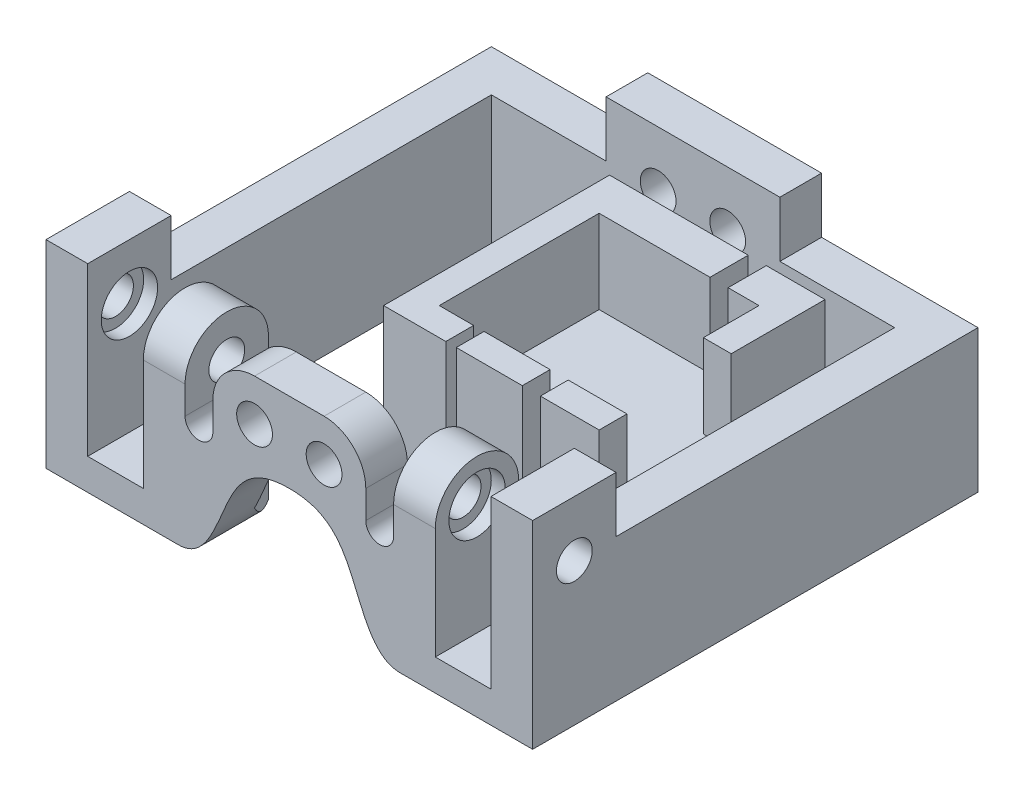
SolidWorks part; units mm, degrees
ref_plane "Front Plane" through (0, 0, 0) normal (0, 0, 1) x (1, 0, 0)
ref_plane "Top Plane" through (0, 0, 0) normal (0, 1, 0) x (1, 0, 0)
ref_plane "Right Plane" through (0, 0, 0) normal (1, 0, 0) x (0, 0, -1)
sketch "Sketch1" plane through (0, 0, 0) normal (0, 1, 0) x (1, 0, 0)
  line L0 (-29, 39) -> (-29, -39)
  line L1 (-35, 45) -> (35, 45)
  line L2 (-35, 45) -> (-35, -45)
  line L3 (-35, -45) -> (35, -45)
  line L4 (35, 45) -> (35, -45)
  line L5 (-29, -39) -> (29, -39)
  line L6 (29, 39) -> (29, -39)
  line L7 (-29, 39) -> (29, 39)
  point P4 (0, 45)
  point P5 (35, 0)
  point P7 (35, 27.1086)
  dimension "D1" = 70
  dimension "D2" = 90
  dimension "D3" = 6
extrude "Boss-Extrude1" add sketch "Sketch1" against normal blind 20.5
sketch "Sketch2" plane through (0, 0, 0) normal (0, -1, 0) x (-1, 0, 0)
  line L0 (-35, 45) -> (35, 45) construction
  line L1 (-12.5, 45) -> (12.5, 45)
  line L2 (-12.5, 45) -> (-12.5, 39)
  line L3 (-12.5, 39) -> (12.5, 39)
  line L4 (12.5, 45) -> (12.5, 39)
  line L5 (-29, 39) -> (29, 39) construction
  point P8 (0, 45)
  point P9 (0, 45)
  dimension "D1" = 25
extrude "Boss-Extrude2" add sketch "Sketch2" against normal blind 8
sketch "Sketch3" plane through (0, 0, -45) normal (0, 0, -1) x (-1, 0, 0)
  line L0 (0, 8) -> (0, 0) construction
  line L1 (12.5, 8) -> (-12.5, 8) construction
  circle A0 centre (-5, 0) radius 2.575
  circle A1 centre (5, 0) radius 2.575
  point P7 (0, 0)
  point P9 (-3.0953, 7.2588)
  point P14 (-18.5119, -15)
  dimension "D1" = 5.15
  dimension "D2" = 5
extrude "Cut-Extrude1" cut sketch "Sketch3" against normal up to next
sketch "Sketch4" plane through (0, 0, -45) normal (0, 0, -1) x (-1, 0, 0)
  line L0 (0, 0) -> (0, 8) construction
  line L1 (-35, 0) -> (35, 0) construction
  line L2 (12.5, 8) -> (-12.5, 8) construction
  circle A0 centre (-5, 0) radius 4.05
  circle A1 centre (-5, 0) radius 2.575 construction
  circle A2 centre (5, 0) radius 4.05
  dimension "D1" = 8.1
extrude "Cut-Extrude2" cut sketch "Sketch4" against normal blind 2
sketch "Sketch5" plane through (0, -20.5, 0) normal (0, 1, 0) x (1, 0, 0)
  line L0 (29, 39) -> (-29, 39) construction
  line L1 (-8, 33.5) -> (15, 33.5)
  line L2 (-8, 33.5) -> (-8, 10.5)
  line L3 (-8, 10.5) -> (15, 10.5)
  line L4 (15, 33.5) -> (15, 10.5)
  line L6 (29, -39) -> (29, 39) construction
  dimension "D1" = 23
  dimension "D2" = 23
  dimension "D3" = 5.5
  dimension "D4" = 14
extrude "Boss-Extrude3" add sketch "Sketch5" along normal offset from surface (7 mm away) 13.5 separate body up to face at (0, 0, -14)
sketch "Sketch16" plane through (0, -20.5, 0) normal (0, -1, 0) x (1, 0, 0)
  line L0 (29, -39) -> (12.5, -39) construction
  line L1 (19, -39) -> (-12, -39)
  line L2 (19, -39) -> (19, -6.5)
  line L3 (19, -6.5) -> (-12, -6.5)
  line L4 (-8, -33.5) -> (15, -33.5)
  line L5 (-8, -10.5) -> (-8, -33.5)
  line L6 (15, -10.5) -> (-8, -10.5)
  line L7 (15, -33.5) -> (15, -10.5)
  line L8 (-8, -33.5) -> (15, -33.5)
  line L9 (-8, -10.5) -> (-8, -33.5)
  line L10 (15, -10.5) -> (-8, -10.5)
  line L11 (15, -33.5) -> (15, -10.5)
  line L12 (-12, -39) -> (-12, -6.5)
  dimension "D2" = 4
  dimension "D3" = 4
  dimension "D4" = 4
  dimension "D1" = 0
extrude "Boss-Extrude6" add sketch "Sketch16" against normal offset from surface (19 mm away) 12 up to face at (3.5, -13.5, -22) offset beyond the face yes
sketch "Sketch18" plane through (0, -1.5, 0) normal (0, 1, 0) x (1, 0, 0)
  line L0 (15, 33.5) -> (-8, 33.5) construction
  line L1 (7.95, 33.5) -> (10.55, 33.5)
  line L2 (7.95, 33.5) -> (7.95, 39)
  line L3 (7.95, 39) -> (10.55, 39)
  line L4 (10.55, 33.5) -> (10.55, 39)
  line L5 (7.093, 39) -> (19, 39) construction
  line L6 (19, 6.5) -> (-12, 6.5) construction
  line L7 (7.95, 6.5) -> (10.55, 6.5)
  line L8 (7.95, 6.5) -> (7.95, 10.5)
  line L9 (7.95, 10.5) -> (10.55, 10.5)
  line L10 (10.55, 6.5) -> (10.55, 10.5)
  line L11 (-8, 10.5) -> (15, 10.5) construction
  line L12 (15, 10.5) -> (-8, 10.5) construction
  line L13 (-3.05, 6.5) -> (-1.55, 6.5)
  line L14 (-3.05, 6.5) -> (-3.05, 10.5)
  line L15 (-3.05, 10.5) -> (-1.55, 10.5)
  line L16 (-1.55, 6.5) -> (-1.55, 10.5)
  line L17 (19, 39) -> (19, 6.5) construction
  line L18 (15, 10.5) -> (19, 10.5)
  line L19 (15, 10.5) -> (15, 25.5)
  line L20 (15, 25.5) -> (19, 25.5)
  line L21 (19, 10.5) -> (19, 25.5)
  line L22 (15, 10.5) -> (15, 33.5) construction
  point P31 (7.95, 36.25)
  dimension "D1" = 15
  dimension "D2" = 4.45
  dimension "D3" = 2.6
  dimension "D4" = 9.5
  dimension "D5" = 1.5
extrude "Cut-Extrude10" cut sketch "Sketch18" against normal up to surface (12 mm away) up to face at (3.5, -13.5, -22)
sketch "gear_alignment_sketch" plane through (35, 0, 0) normal (1, 0, 0) x (0, 0, -1)
  line L0 (16.5, 0) -> (16.5, -20.5) construction
  line L1 (-45, 0) -> (45, 0) construction
  line L2 (-45, -20.5) -> (45, -20.5) construction
  line L3 (-992.2945, 0) -> (49007.7055, 0) construction
  line L5 (-45, 0) -> (45, 0) construction
  line L7 (-13.0635, 0) -> (16.5, -7.5) construction
  line L8 (25.5, -13.5) -> (33.5, -13.5) construction
  point P7 (-13.0635, 0)
  point P10 (16.5, -7.5)
  point P11 (0, 0)
  dimension "D1" = 6
  dimension "D3" = 30.5
  dimension "D2" = 6
sketch "Sketch8" plane through (0, 0, 0) normal (0, 1, 0) x (1, 0, 0)
  line L0 (35, -200992.2945) -> (35, 249007.7055) construction
  line L1 (35, -7.0635) -> (29, -7.0635)
  line L2 (35, -7.0635) -> (35, -19.0635)
  line L3 (35, -19.0635) -> (29, -19.0635)
  line L4 (29, -7.0635) -> (29, -19.0635)
  line L5 (29, -39) -> (29, 39) construction
  dimension "D1" = 12
extrude "Boss-Extrude4" add sketch "Sketch8" along normal blind 8
sketch "Sketch7" plane through (35, 0, 0) normal (1, 0, 0) x (0, 0, -1)
  circle A0 centre (-13.0635, 0) radius 2.575
  dimension "D1" = 5.15
extrude "x" cut sketch "Sketch7" against normal up to next
sketch "Sketch9" plane through (29, 0, 0) normal (1, 0, 0) x (0, 0, -1)
  circle A0 centre (-13.0635, 0) radius 4.05
  dimension "D1" = 8.1
extrude "Cut-Extrude4" cut sketch "Sketch9" along normal blind 2
sketch "Sketch10" plane through (0, -20.5, 0) normal (0, -1, 0) x (1, 0, 0)
  line L1 (0, 7.0635) -> (29, 7.0635)
  line L3 (0, 19.0635) -> (29, 19.0635)
  line L4 (29, 7.0635) -> (29, 19.0635)
  line L5 (29, 39) -> (29, -39) construction
  line L6 (35, 7.0635) -> (29, 7.0635) construction
  line L7 (29, 19.0635) -> (35, 19.0635) construction
  line L8 (0, -1000) -> (0, 49000) construction
  line L9 (0, 7.0635) -> (0, 19.0635)
extrude "Boss-Extrude5" add sketch "Sketch10" against normal up to surface (28.5 mm away) up to face at (32, 8, 13.0635)
sketch "Sketch12" plane through (0, 8, 0) normal (0, 1, 0) x (1, 0, 0)
  line L0 (0, -19.0635) -> (35, -19.0635) construction
  line L1 (29, -7.0635) -> (21, -7.0635)
  line L2 (29, -7.0635) -> (29, -19.0635)
  line L3 (29, -19.0635) -> (21, -19.0635)
  line L4 (21, -7.0635) -> (21, -19.0635)
  line L5 (35, -7.0635) -> (0, -7.0635) construction
  line L6 (15, -7.0635) -> (0, -7.0635)
  line L7 (15, -7.0635) -> (15, -19.0635)
  line L8 (15, -19.0635) -> (0, -19.0635)
  line L9 (0, -7.0635) -> (0, -19.0635)
  dimension "D1" = 8
  dimension "D2" = 6
extrude "Cut-Extrude6" cut sketch "Sketch12" against normal blind 24
sketch "Sketch13" plane through (21, 0, 0) normal (1, 0, 0) x (0, 0, -1)
  circle A0 centre (-13.0635, 0) radius 2.575
  circle A1 centre (-13.0635, 0) radius 2.575 construction
extrude "Cut-Extrude7" cut sketch "Sketch13" against normal up to next
sketch "Sketch14" plane through (21, 0, 0) normal (1, 0, 0) x (0, 0, -1)
  circle A0 centre (-13.0635, 0) radius 4.05
  circle A1 centre (-13.0635, 0) radius 4.05 construction
extrude "Cut-Extrude8" cut sketch "Sketch14" against normal blind 2
sketch "Sketch15" plane through (21, 0, 0) normal (1, 0, 0) x (0, 0, -1)
  line L0 (-7.0635, 8) -> (-7.0635, 0) construction
  line L1 (-19.0635, 0) -> (-19.0635, 8)
  line L2 (-19.0635, 8) -> (-7.0635, 8)
  line L3 (-7.0635, 8) -> (-7.0635, 0)
  arc A0 (-19.0635, 0) -> (-7.0635, 0) centre (-13.0635, 0) cw
extrude "Cut-Extrude9" cut sketch "Sketch15" against normal up to next
sketch "Sketch23" plane through (0, -16, 0) normal (0, 1, 0) x (1, 0, 0)
  line L1 (0, -13.0635) -> (11, -13.0635)
  line L2 (0, -13.0635) -> (0, -19.0635)
  line L3 (0, -19.0635) -> (11, -19.0635)
  line L4 (11, -13.0635) -> (11, -19.0635)
  line L5 (0, -1000) -> (0, 49000) construction
  line L7 (21, -19.0635) -> (29, -19.0635) construction
  dimension "D1" = 11
  dimension "D2" = 6
extrude "Boss-Extrude8" add sketch "Sketch23" along normal offset from surface (22 mm away) 6 up to face at (25.5, 0, -25.6455) offset beyond the face yes
sketch "Sketch21" plane through (0, 0, 7.0635) normal (0, 0, -1) x (-1, 0, 0)
  circle A0 centre (-5, 0) radius 2.575
  circle A1 centre (-5, 0) radius 2.575 construction
extrude "Cut-Extrude12" cut sketch "Sketch21" against normal up to next
sketch "Sketch22" plane through (0, 0, 13.0635) normal (0, 0, -1) x (-1, 0, 0)
  circle A0 centre (-5, 0) radius 4.05
  circle A1 centre (-5, 0) radius 4.05 construction
extrude "Cut-Extrude13" cut sketch "Sketch22" against normal blind 2
sketch "Sketch25" plane through (0, 0, 19.0635) normal (0, 0, 1) x (1, 0, 0)
  line L0 (5, 6) -> (11, 6)
  line L1 (0, 6) -> (11, 6) construction
  line L2 (11, 6) -> (11, 0)
  arc A0 (11, 0) -> (5, 6) centre (5, 0) ccw
extrude "Cut-Extrude14" cut sketch "Sketch25" against normal up to next
sketch "Sketch26" plane through (0, 0, 19.0635) normal (0, 0, 1) x (1, 0, 0)
  line L0 (15, -16) -> (15, 0) construction
  line L1 (11, 0) -> (11, -16) construction
  line L3 (11, -4) -> (11, -16)
  line L4 (11, -16) -> (15, -16)
  line L5 (11, -16) -> (15, -16) construction
  line L6 (15, -16) -> (15, -4)
  arc A0 (15, -4) -> (11, -4) centre (13, -4) cw
  dimension "D1" = 4
extrude "Boss-Extrude9" add sketch "Sketch26" against normal up to surface (12 mm away) up to face at (16.25, -13.125, 7.0635)
sketch "Sketch19" plane through (0, 0, 0) normal (0, 1, 0) x (1, 0, 0)
  line L1 (-35, -45) -> (35, -45)
  line L2 (-35, -45) -> (-35, -19.0635)
  line L3 (-35, -19.0635) -> (35, -19.0635)
  line L4 (35, -45) -> (35, -19.0635)
extrude "Cut-Extrude11" cut sketch "Sketch19" against normal through all
sketch "Sketch27" plane through (0, 6, 0) normal (0, 1, 0) x (1, 0, 0)
  line L0 (15, -7.0635) -> (11, -13.0635)
  line L1 (11, -13.0635) -> (0, -13.0635)
  line L2 (0, -13.0635) -> (0, -7.0635)
  line L3 (0, -7.0635) -> (15, -7.0635)
extrude "Cut-Extrude15" cut sketch "Sketch27" against normal up to next
sketch "Sketch28" plane through (0, 0, 19.0635) normal (0, 0, 1) x (1, 0, 0)
  line L0 (0, 6) -> (0, -20.5) construction
  line L1 (35, -20.5) -> (0, -20.5) construction
  line L2 (19.0278, -20.5) -> (12.909, -20.5) construction
  line L3 (3.0234, -5.5) -> (-3.0524, -5.5) construction
  line L4 (0, -5.5) -> (0, -20.5)
  line L5 (0, -20.5) -> (15.9684, -20.5)
  arc A0 (11, 0) -> (5, 6) centre (5, 0) ccw construction
  spline S0 degree 3 poles (0, -5.5) (5.7847, -5.5) (9.4044, -11.9209) (12.3084, -20.5) (15.9684, -20.5) knots 0 0 0 0 0.502636 1 1 1 1
  point P2 (0, 0)
  point P12 (0, -5.4859)
  point P18 (9.2426, 4.2426)
  dimension "D2" = 1.5
  dimension "D1" = 8
extrude "Cut-Extrude16" cut sketch "Sketch28" against normal up to next
mirror "Mirror1" about plane through (0, 0, 0) normal (1, 0, 0) of "Cut-Extrude16", "Cut-Extrude15", "Cut-Extrude11", "Boss-Extrude9", "Cut-Extrude13", "Cut-Extrude12", "Boss-Extrude8", "Cut-Extrude4", "x", "Boss-Extrude4", "Boss-Extrude5", "Cut-Extrude6", "Cut-Extrude7", "Cut-Extrude8", "Cut-Extrude9", "Cut-Extrude14"
equation "\"bushing_hole_outer_diameter\"= 8.1mm"
equation "\"bushing_hole_inner_diameter\"= 5.15mm"
equation "\"D1@Sketch3\"=\"bushing_hole_inner_diameter\""
equation "\"D1@Sketch4\"=\"bushing_hole_outer_diameter\""
equation "\"bushing_flange_depth\"= 2mm"
equation "\"D1@Cut-Extrude2\"=\"bushing_flange_depth\""
equation "\"D1@Boss-Extrude3\"=12+1.5"
equation "\"gear_spacing\"= 30.5mm"
equation "\"D3@gear_alignment_sketch\" = \"gear_spacing\""
equation "\"D1@Sketch7\"=\"bushing_hole_inner_diameter\""
equation "\"D1@Sketch9\"=\"bushing_hole_outer_diameter\""
equation "\"D1@Cut-Extrude4\"=\"bushing_flange_depth\""
equation "\"D1@Cut-Extrude8\"=\"bushing_flange_depth\""
equation "\"D1@Cut-Extrude13\"=\"bushing_flange_depth\""
